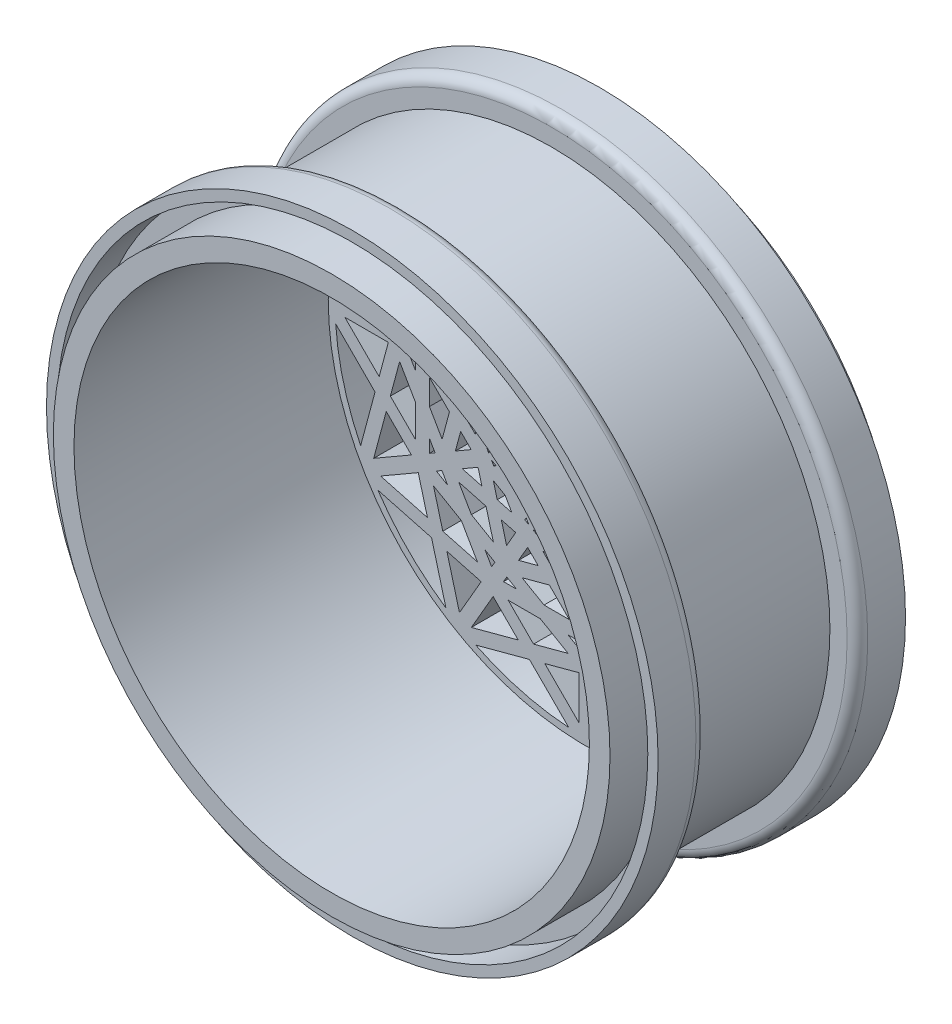
SolidWorks part; units mm, degrees
ref_plane "Front Plane" through (0, 0, 0) normal (0, 0, 1) x (1, 0, 0)
ref_plane "Top Plane" through (0, 0, 0) normal (0, 1, 0) x (1, 0, 0)
ref_plane "Right Plane" through (0, 0, 0) normal (1, 0, 0) x (0, 0, -1)
sketch "Sketch1" plane through (0, 0, 0) normal (0, 0, 1) x (1, 0, 0)
  circle A0 centre (0, 0) radius 40.5
  circle A1 centre (0, 0) radius 37.5
  dimension "D1" = 81
  dimension "D2" = 3
extrude "Boss-Extrude1" add sketch "Sketch1" along normal blind 36 contours A0 A1 region at (-39.3545, 0, 0)
sketch "Sketch2" plane through (0, 0, 0) normal (0, 0, -1) x (-1, 0, 0)
  circle A0 centre (0, 0) radius 40.5
  circle A1 centre (0, 0) radius 44.5
  circle A2 centre (0, 0) radius 40.5 construction
  circle M3 centre (0, 0) radius 37.5
  circle M4 centre (0, 0) radius 40.5
  dimension "D1" = 89
extrude "Boss-Extrude2" add sketch "Sketch2" along normal blind 3 contours A1 M4 | M3 | M4 M3 region at (39.3545, 0, 0) region at (43.2413, 0, 0) region at (0, 0, 0)
sketch "Sketch3" plane through (0, 0, 36) normal (0, 0, 1) x (1, 0, 0)
  circle A0 centre (0, 0) radius 37.5
  circle A1 centre (0, 0) radius 44.5
  circle A2 centre (0, 0) radius 37.5 construction
  dimension "D1" = 89
extrude "Boss-Extrude3" add sketch "Sketch3" along normal blind 3
sketch "Sketch4" plane through (0, 0, -3) normal (0, 0, -1) x (-1, 0, 0)
  circle A0 centre (0, 0) radius 5
  dimension "D1" = 10
extrude "Cut-Extrude1" cut sketch "Sketch4" against normal up to surface (3 mm away) up to face at (40.5, 0, 0)
sketch "Sketch5" plane through (0, 0, -3) normal (0, 0, -1) x (-1, 0, 0)
  circle A0 centre (0, 0) radius 37.5
  dimension "D1" = 75
extrude "Cut-Extrude2" cut sketch "Sketch5" against normal blind 1
sketch "Sketch6" plane through (0, 0, -2) normal (0, 0, -1) x (-1, 0, 0)
  line L0 (0, 0) -> (0, 37.5)
  line L1 (0, 0) -> (18.75, 32.476)
  line L2 (0, 0) -> (-18.75, 32.476)
  line L3 (-18.75, 32.476) -> (0, 27.4519)
  line L4 (0, 27.4519) -> (-11.887, 20.5889)
  line L5 (-11.887, 20.5889) -> (0, 17.4038)
  line L6 (0, 17.4038) -> (-7.5361, 13.0529)
  line L7 (-7.5361, 13.0529) -> (0, 11.0336)
  line L8 (0, 37.5) -> (-13.726, 23.774)
  line L9 (-13.726, 23.774) -> (0, 23.774)
  line L10 (0, 23.774) -> (-8.7019, 15.0721)
  line L11 (-8.7019, 15.0721) -> (0, 15.0721)
  line L12 (0, 15.0721) -> (-5.5168, 9.5554)
  line L13 (-16.0421, 32.7857) -> (-8.2235, 30.6907)
  line L14 (-8.2235, 30.6907) -> (-2.4999, 36.4143)
  line L15 (-16.6769, 30.8852) -> (-13.5115, 25.4027)
  line L16 (-13.5115, 25.4027) -> (-9.8565, 29.0577)
  line L17 (-9.8565, 29.0577) -> (-16.6769, 30.8852)
  line L18 (-5.9928, 30.093) -> (-1, 28.7551)
  line L19 (-1, 28.7551) -> (-1, 35.0858)
  line L20 (-1, 35.0858) -> (-5.9928, 30.093)
  line L21 (-11.3117, 24.774) -> (-7.6258, 28.46)
  line L22 (-7.6258, 28.46) -> (-2.5908, 27.1108)
  line L23 (-2.5908, 27.1108) -> (-6.6382, 24.774)
  line L24 (-6.6382, 24.774) -> (-11.3117, 24.774)
  line L25 (-11.9939, 22.774) -> (-11.521, 21.955)
  line L26 (-11.521, 21.955) -> (-10.1023, 22.774)
  line L27 (-10.1023, 22.774) -> (-11.9939, 22.774)
  line L28 (-1, 25.7199) -> (-2.6382, 24.774)
  line L29 (-2.6382, 24.774) -> (-1, 24.774)
  line L30 (-1, 24.774) -> (-1, 25.7199)
  line L31 (-9.2963, 20.93) -> (-6.1023, 22.774)
  line L32 (-6.1023, 22.774) -> (-2.4142, 22.774)
  line L33 (-2.4142, 22.774) -> (-5.3229, 19.8654)
  line L34 (-5.3229, 19.8654) -> (-9.2963, 20.93)
  line L35 (-9.8139, 18.9982) -> (-8.4875, 16.7008)
  line L36 (-8.4875, 16.7008) -> (-6.9559, 18.2324)
  line L37 (-6.9559, 18.2324) -> (-9.8139, 18.9982)
  line L38 (-3.0922, 19.2676) -> (-1, 18.707)
  line L39 (-1, 18.707) -> (-1, 21.3598)
  line L40 (-1, 21.3598) -> (-3.0922, 19.2676)
  line L41 (-4.7252, 17.6346) -> (-6.2877, 16.0721)
  line L42 (-6.2877, 16.0721) -> (-4.3065, 16.0721)
  line L43 (-4.3065, 16.0721) -> (-2.5908, 17.0627)
  line L44 (-2.5908, 17.0627) -> (-4.7252, 17.6346)
  line L45 (-6.9699, 14.0721) -> (-7.17, 14.4189)
  line L46 (-7.17, 14.4189) -> (-7.7706, 14.0721)
  line L47 (-7.7706, 14.0721) -> (-6.9699, 14.0721)
  line L48 (-4.9453, 13.3939) -> (-3.484, 13.0024)
  line L49 (-3.484, 13.0024) -> (-2.4142, 14.0721)
  line L50 (-2.4142, 14.0721) -> (-3.7706, 14.0721)
  line L51 (-3.7706, 14.0721) -> (-4.9453, 13.3939)
  line L52 (-1, 15.6718) -> (-1, 16.0721)
  line L53 (-1, 16.0721) -> (-0.3065, 16.0721)
  line L54 (-0.3065, 16.0721) -> (-1, 15.6718)
  line L55 (-1, 12.6579) -> (-1.2533, 12.4047)
  line L56 (-1.2533, 12.4047) -> (-1, 12.3368)
  line L57 (-1, 12.3368) -> (-1, 12.6579)
  line L58 (-2.8863, 10.7717) -> (-3.1054, 10.5526)
  line L59 (-2.8863, 10.7717) -> (-2.587, 10.6915)
  line L60 (-5.4629, 11.4621) -> (-5.3024, 11.184)
  line L61 (-5.3024, 11.184) -> (-5.117, 11.3694)
  line L62 (-5.117, 11.3694) -> (-5.4629, 11.4621)
  circle A0 centre (0, 0) radius 37.5 construction
  circle A1 centre (0, 0) radius 11
  circle A2 centre (0, 0) radius 5 construction
  circle A3 centre (0, 0) radius 36.5
  circle M67 centre (0, 0) radius 37.5
  circle M68 centre (0, 0) radius 5
  dimension "D1" = 30
  dimension "D2" = 6
  dimension "D3" = 45
  dimension "D4" = 45
  dimension "D5" = 1
  dimension "D6" = 1
  dimension "D7" = 1
  dimension "D8" = 1
  dimension "D9" = 1
  dimension "D10" = 1
  dimension "D11" = 1
  dimension "D12" = 1
  dimension "D13" = 1
  dimension "D14" = 1
  dimension "D15" = 1
  dimension "D16" = 1
  dimension "D17" = 1
  dimension "D18" = 1
  dimension "D19" = 1
  dimension "D20" = 1
  dimension "D21" = 1
  dimension "D22" = 1
  dimension "D23" = 1
  dimension "D24" = 1
  dimension "D25" = 1
  dimension "D26" = 1
  dimension "D27" = 1
  dimension "D28" = 1
  dimension "D29" = 1
  dimension "D30" = 1
  dimension "D31" = 1
  dimension "D32" = 1
  dimension "D33" = 1
  dimension "D34" = 1
  dimension "D35" = 1
  dimension "D36" = 1
  dimension "D37" = 1
  dimension "D38" = 1
  dimension "D39" = 1
  dimension "D40" = 1
  dimension "D41" = 1
  dimension "D42" = 1
  dimension "D43" = 1
  dimension "D44" = 1
  dimension "D45" = 1
  dimension "D46" = 1
  dimension "D47" = 1
  dimension "D48" = 1
  dimension "D49" = 1
  dimension "D50" = 1
  dimension "D51" = 1
  dimension "D52" = 1
  dimension "D53" = 1
extrude "Cut-Extrude3" cut sketch "Sketch6" against normal up to surface (2 mm away) contours L14 A3 L13 | L16 L17 L15 | L19 L20 L18 | L24 L23 L22 L21 | L29 L30 L28 | L26 L27 L25 | L34 L33 L32 L31 | L36 L37 L35 | L39 L40 L38 | L43 L44 L41 L42 | L50 L51 L48 L49 | L56 L57 L55 | L61 L62 L60 | A1 L59 L58 region at (2.8599, 10.6733, -2) region at (8.9987, 33.5837, -2) region at (13.3483, 28.4485, -2) region at (2.6643, 31.3113, -2) region at (7.0718, 26.3921, -2) region at (11.2057, 22.501, -2) region at (1.5461, 25.0893, -2) region at (5.7601, 21.4971, -2) region at (8.4191, 17.9771, -2) region at (1.6974, 19.7782, -2) region at (4.4903, 16.7581, -2) region at (3.6448, 13.6025, -2) region at (1.0844, 12.4665, -2) region at (5.2941, 11.3385, -2) up to face at (-5, 0, 0)
pattern_circular "CirPattern1" count 12 every 30 about axis through (0, 0, -2) along (0, 0, 1) of "Cut-Extrude3"
extrude "Boss-Extrude4" add sketch "Sketch6<4>" along normal up to surface (1 mm away) and the other way blind 4 contours A3 L8 L3 M67 | A3 L0 L8 | A3 L3 L2 | L3 A3 L2 L8 L17 L16 L15 | L8 A3 L14 L13 L3 | L0 A3 L8 L3 L20 L19 L18 | L8 L9 L4 L3 L23 L24 L21 L22 | L9 L2 L4 L27 L26 L25 | L4 L9 L0 L30 L29 L28 | L10 L9 L4 L5 L33 L34 L31 L32 | L0 L10 L5 L40 L39 L38 | L10 L5 L2 L37 L36 L35 | L10 L11 L6 L5 L44 L43 L42 L41 | L6 L11 L0 L53 L54 L52 | L11 L2 L6 L47 L46 L45 | L12 L11 L6 L7 L51 L50 L49 L48 | L0 L12 L7 L57 L56 L55 | L12 L7 L2 L62 L61 L60 | A1 L0 L7 L12 L2 L58 L59 | L0 A1 L2 M68 region at (1.0616, 12.6655, -2) region at (2.9398, 10.9715, -2) region at (1.3637, 15.8467, -2) region at (1.6504, 13.5374, -2) region at (2.1429, 7.9975, -2) region at (5.4134, 11.4994, -2) region at (2.491, 18.1553, -2) region at (2.0665, 16.3198, -2) region at (6.7423, 14.4055, -2) region at (3.1851, 23.8476, -2) region at (2.6033, 21.3533, -2) region at (6.9252, 16.9733, -2) region at (3.9312, 28.6298, -2) region at (3.2596, 25.742, -2) region at (9.1687, 22.2509, -2) region at (0.3372, 36.8302, -2) region at (10.9191, 26.7685, -2) region at (12.5988, 31.0115, -2) region at (9.4809, 35.3833, -2) region at (18.1231, 32.0645, -2) up to face at (-37.5, 0, -3)
sketch "Sketch6<4>" plane through (0, 0, -2) normal (0, 0, -1) x (-1, 0, 0) same geometry as "Sketch6"
pattern_circular "CirPattern2" count 12 every 30 about axis through (0, 0, -3) along (0, 0, -1) of "Boss-Extrude4"
sketch "Sketch7" plane through (0, 0, -3) normal (0, 0, -1) x (-1, 0, 0)
  line L0 (0, 0) -> (0, 8.9745)
  line L1 (0, 0) -> (-2.0706, 7.7274)
  circle A0 centre (0, 0) radius 5.5
  circle A1 centre (-2.0706, 7.7274) radius 1.5
  circle A2 centre (5.6569, 5.6569) radius 1.5
  circle A3 centre (7.7274, -2.0706) radius 1.5
  circle A4 centre (2.0706, -7.7274) radius 1.5
  circle A5 centre (-5.6569, -5.6569) radius 1.5
  circle A6 centre (-7.7274, 2.0706) radius 1.5
  point P19 (0, 0)
  dimension "D1" = 3
  dimension "D2" = 11
  dimension "D3" = 8
  dimension "D4" = 15
  dimension "D5" = 6
extrude "Cut-Extrude4" cut sketch "Sketch7" against normal up to surface (5 mm away) contours A1 | A2 | A3 | A4 | A5 | A6 | L1 A0 L0 | L0 A0 L1 region at (0.4772, 3.6249, -3) region at (-0.0207, -0.1576, -3) region at (3.2269, 8.6147, -3) region at (-5.6569, 5.6569, -3) region at (-7.7274, -2.0706, -3) region at (-2.0706, -7.7274, -3) region at (5.6569, -5.6569, -3) region at (7.7274, 2.0706, -3) up to face at (-37.5, 0, 2)
ref_plane "Plane1" through (0, 0, -0.5) normal (0, 0, -1) x (-1, 0, 0)
sketch "Sketch10" plane through (0, 0, -3) normal (0, 0, -1) x (-1, 0, 0)
  line L0 (0, 0) -> (0, 36.5)
  circle A0 centre (0, 0) radius 36.5
  arc A1 (-2.4999, 36.4143) -> (-16.0421, 32.7857) centre (0, 0) ccw construction
sketch3d "3DSketch3"
  line L0 (0, 0, -0.5) -> (0, 0, -535.9)
  circle A0 centre (0, 0, -3) radius 5.5 construction
  arc A1 (0, 0, -0.5) -> (0, 0, -535.9) centre (0, 0, -268.2) cw
  point P5 (0, 0, -8.5)
  point P8 (-267.7, 0, -268.2)
sweep "Cut-Sweep4" cut profiles "3DSketch3" path "Sketch10"
sketch "Sketch11" plane through (0, 0, 0) normal (0, 0, 1) x (1, 0, 0)
  circle A0 centre (0, 0) radius 40.5
  circle A1 centre (0, 0) radius 40.5 construction
  circle A2 centre (0, 0) radius 44.5
  circle A3 centre (0, 0) radius 44.5 construction
extrude "Boss-Extrude5" add sketch "Sketch11" along normal blind 7
sketch "Sketch12" plane through (0, 0, 36) normal (0, 0, -1) x (-1, 0, 0)
  circle A0 centre (0, 0) radius 40.5
  circle A1 centre (0, 0) radius 40.5 construction
  circle A2 centre (0, 0) radius 44.5
  circle A3 centre (0, 0) radius 44.5 construction
extrude "Boss-Extrude6" add sketch "Sketch12" along normal blind 7
sketch "Sketch13" plane through (0, 0, -3) normal (0, 0, -1) x (-1, 0, 0)
  circle A0 centre (0, 0) radius 40.5
  circle A1 centre (0, 0) radius 44.5
  circle A2 centre (0, 0) radius 44.5 construction
  dimension "D1" = 81
extrude "Cut-Extrude5" cut sketch "Sketch13" against normal blind 3
sketch "Sketch14" plane through (0, 0, 39) normal (0, 0, 1) x (1, 0, 0)
  circle A0 centre (0, 0) radius 40.5
  circle A1 centre (0, 0) radius 44.5
  circle A2 centre (0, 0) radius 44.5 construction
  dimension "D1" = 81
extrude "Cut-Extrude6" cut sketch "Sketch14" against normal blind 3
sketch "Sketch15" plane through (0, 0, 0) normal (0, 0, -1) x (-1, 0, 0)
  circle A0 centre (0, 0) radius 40.5
  circle A1 centre (0, 0) radius 43
  circle A2 centre (0, 0) radius 40.5 construction
  circle A3 centre (0, 0) radius 44.5 construction
  dimension "D1" = 1.5
extrude "Cut-Extrude7" cut sketch "Sketch15" against normal offset from surface (5 mm away) 2 up to face at (44.5, 0, 7)
sketch "Sketch16" plane through (0, 0, 36) normal (0, 0, 1) x (1, 0, 0)
  circle A0 centre (0, 0) radius 40.5
  circle A1 centre (0, 0) radius 43
  circle A2 centre (0, 0) radius 40.5 construction
  circle A3 centre (0, 0) radius 44.5 construction
  dimension "D1" = 1.5
extrude "Cut-Extrude8" cut sketch "Sketch16" against normal offset from surface (5 mm away) 2 up to face at (-44.5, 0, 29)
fillet "Fillet1" radius 1.5 2 edges at (-44.5, 0, 29) (44.5, 0, 7)
equation "\"spokewidth\"=1"
equation "\"D6@Sketch6\"=\"spokewidth\""
equation "\"D7@Sketch6\"=\"spokewidth\""
equation "\"D8@Sketch6\"=\"spokewidth\""
equation "\"D9@Sketch6\"=\"spokewidth\""
equation "\"D10@Sketch6\"=\"spokewidth\""
equation "\"D11@Sketch6\"=\"spokewidth\""
equation "\"D12@Sketch6\"=\"spokewidth\""
equation "\"D13@Sketch6\"=\"spokewidth\""
equation "\"D14@Sketch6\"=\"spokewidth\""
equation "\"D15@Sketch6\"=\"spokewidth\""
equation "\"D16@Sketch6\"=\"spokewidth\""
equation "\"D17@Sketch6\"=\"spokewidth\""
equation "\"D18@Sketch6\"=\"spokewidth\""
equation "\"D19@Sketch6\"=\"spokewidth\""
equation "\"D20@Sketch6\"=\"spokewidth\""
equation "\"D21@Sketch6\"=\"spokewidth\""
equation "\"D22@Sketch6\"=\"spokewidth\""
equation "\"D23@Sketch6\"=\"spokewidth\""
equation "\"D24@Sketch6\"=\"spokewidth\""
equation "\"D25@Sketch6\"=\"spokewidth\""
equation "\"D26@Sketch6\"=\"spokewidth\""
equation "\"D27@Sketch6\"=\"spokewidth\""
equation "\"D28@Sketch6\"=\"spokewidth\""
equation "\"D29@Sketch6\"=\"spokewidth\""
equation "\"D30@Sketch6\"=\"spokewidth\""
equation "\"D31@Sketch6\"=\"spokewidth\""
equation "\"D32@Sketch6\"=\"spokewidth\""
equation "\"D33@Sketch6\"=\"spokewidth\""
equation "\"D34@Sketch6\"=\"spokewidth\""
equation "\"D35@Sketch6\"=\"spokewidth\""
equation "\"D36@Sketch6\"=\"spokewidth\""
equation "\"D37@Sketch6\"=\"spokewidth\""
equation "\"D38@Sketch6\"=\"spokewidth\""
equation "\"D39@Sketch6\"=\"spokewidth\""
equation "\"D40@Sketch6\"=\"spokewidth\""
equation "\"D41@Sketch6\"=\"spokewidth\""
equation "\"D42@Sketch6\"=\"spokewidth\""
equation "\"D43@Sketch6\"=\"spokewidth\""
equation "\"D44@Sketch6\"=\"spokewidth\""
equation "\"D45@Sketch6\"=\"spokewidth\""
equation "\"D46@Sketch6\"=\"spokewidth\""
equation "\"D47@Sketch6\"=\"spokewidth\""
equation "\"D48@Sketch6\"=\"spokewidth\""
equation "\"D49@Sketch6\"=\"spokewidth\""
equation "\"D50@Sketch6\"=\"spokewidth\""
equation "\"D51@Sketch6\"=\"spokewidth\""
equation "\"D52@Sketch6\"=\"spokewidth\""
equation "\"D53@Sketch6\"=\"spokewidth\""
